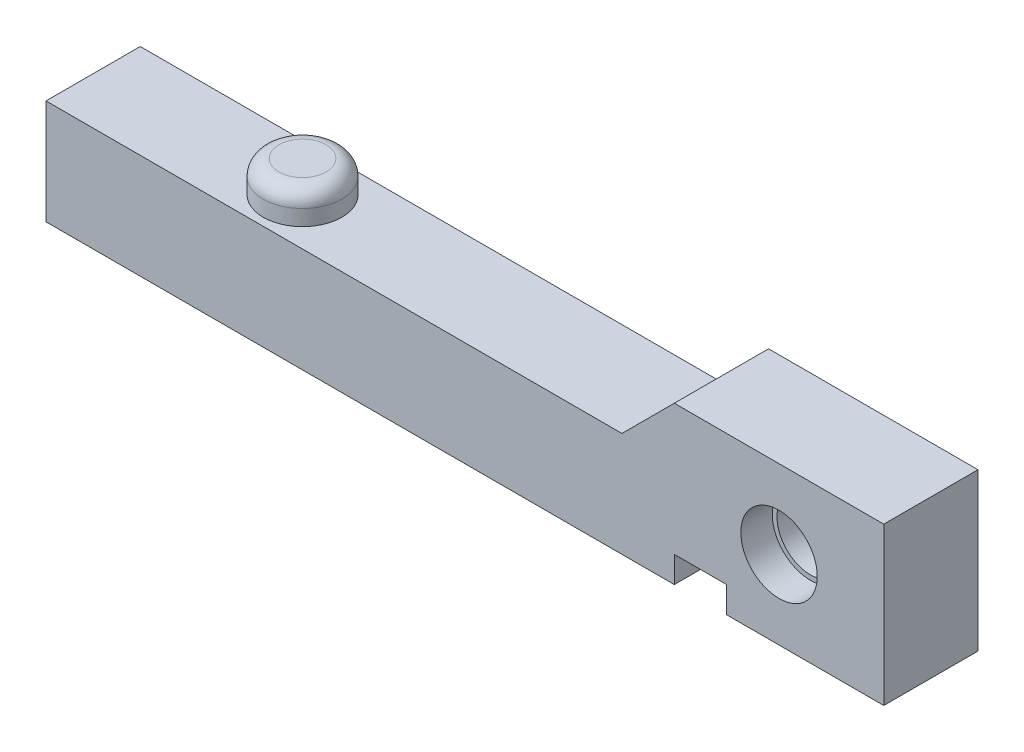
SolidWorks part; units mm, degrees
ref_plane "Спереди" through (0, 0, 0) normal (0, 0, 1) x (1, 0, 0)
ref_plane "Сверху" through (0, 0, 0) normal (0, 1, 0) x (1, 0, 0)
ref_plane "Справа" through (0, 0, 0) normal (1, 0, 0) x (0, 0, -1)
sketch "Эскиз1" plane through (0, 0, 0) normal (0, 0, 1) x (1, 0, 0)
  line L0 (0, 10) -> (55, 10)
  line L1 (55, 10) -> (60, 15)
  line L2 (60, 15) -> (80, 15)
  line L3 (80, 15) -> (80, 0)
  line L4 (80, 0) -> (65, 0)
  line L5 (0, 0) -> (0, 10)
  line L9 (13, 0) -> (0, 0)
  line L10 (60, 0) -> (60, 2.5)
  line L11 (60, 2.5) -> (65, 2.5)
  line L12 (65, 2.5) -> (65, 0)
  line L13 (60, 0) -> (13, 0)
  circle A0 centre (70, 7.5) radius 3.2
  point P8 (70, 15)
  point P12 (12.6355, 0)
  point P13 (80, 7.5)
  point P17 (34, 2.5)
  point P20 (41.5389, 2.5)
  point P21 (0, 0)
  dimension "D6" = 6.4
  dimension "D1" = 10
  dimension "D2" = 55
  dimension "D3" = 80
  dimension "D4" = 15
  dimension "D5" = 45
  dimension "D10" = 15
extrude "Основа" add sketch "Эскиз1" along normal blind 4.5 and the other way blind 4.5
sketch "Эскиз2" [suppressed] plane through (0, 10, 0) normal (0, 1, 0) x (1, 0, 0)
  line L0 (0, -4.5) -> (0, 4.5) construction
  circle A0 centre (27, 0) radius 3.75
  point P5 (0, 0)
  dimension "D1" = 7.5
  dimension "D2" = 27
extrude "Буёк по центру" [suppressed] add sketch "Эскиз2" along normal blind 5
fillet "Скругление2" [suppressed] radius 1.5
sketch "Эскиз3" plane through (0, 0, 4.5) normal (0, 0, 1) x (1, 0, 0)
  circle A0 centre (70, 7.5) radius 3.65
  dimension "D1" = 7.3
extrude "Углубление под подшипник" cut sketch "Эскиз3" against normal blind 3
mirror "Зеркальное отражение1" about plane through (0, 0, 0) normal (0, 0, 1) of "Углубление под подшипник"
sketch "Эскиз5" plane through (0, 10, 0) normal (0, 1, 0) x (1, 0, 0)
  line L1 (0, 4.5) -> (0, -4.5) construction
  circle A0 centre (20, 0) radius 3.75
  point P2 (15.31, 0)
  point P4 (8.0432, 0)
  dimension "D1" = 7.5
  dimension "D2" = 20
extrude "буёк с краю" add sketch "Эскиз5" along normal blind 3
fillet "Скругление3" radius 1.5 1 edges at (20, 13, 3.75)
